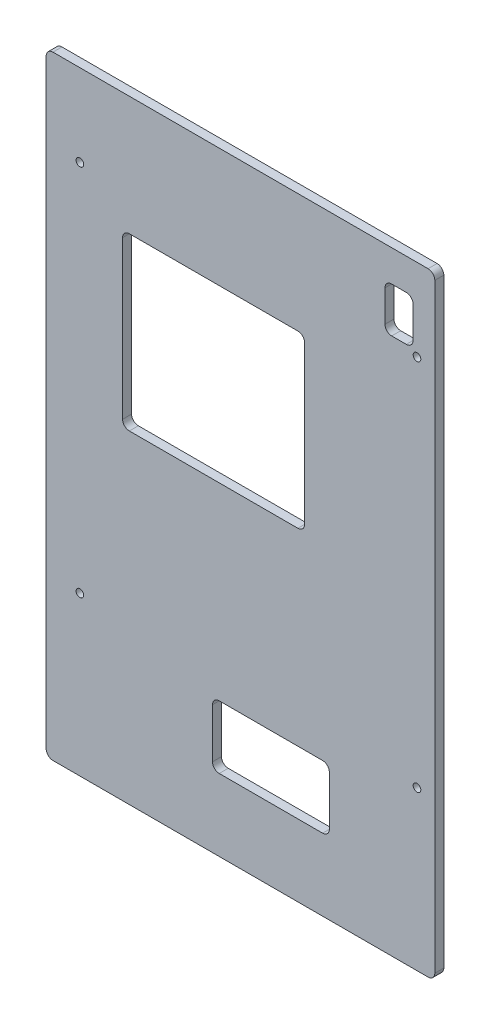
SolidWorks part; units mm, degrees
material "Verre"
ref_plane "Plan de face" through (0, 0, 0) normal (0, 0, 1) x (1, 0, 0)
ref_plane "Plan de dessus" through (0, 0, 0) normal (0, 1, 0) x (1, 0, 0)
ref_plane "Plan de droite" through (0, 0, 0) normal (1, 0, 0) x (0, 0, -1)
sketch "Esquisse1" plane through (0, 0, 0) normal (0, 0, 1) x (1, 0, 0)
  line L1 (0, 0) -> (172.93, 0)
  line L2 (0, 0) -> (0, 273)
  line L3 (0, 273) -> (172.93, 273)
  line L4 (172.93, 0) -> (172.93, 273)
  line L5 (74, 60) -> (126, 60)
  line L6 (74, 60) -> (74, 32)
  line L7 (74, 32) -> (126, 32)
  line L8 (126, 60) -> (126, 32)
  line L9 (34, 220) -> (115, 220)
  line L10 (34, 220) -> (34, 144)
  line L11 (34, 144) -> (115, 144)
  line L12 (115, 220) -> (115, 144)
  line L13 (163.25, 259) -> (150.75, 259)
  line L14 (163.25, 259) -> (163.25, 239)
  line L15 (163.25, 239) -> (150.75, 239)
  line L16 (150.75, 259) -> (150.75, 239)
  line L17 (163.25, 259) -> (150.75, 239) construction
  line L18 (163.25, 239) -> (150.75, 259) construction
  circle A0 centre (15, 236.5) radius 1.5
  circle A1 centre (165, 236.5) radius 1.5
  circle A2 centre (15, 70.5) radius 1.5
  circle A3 centre (165, 70.5) radius 1.5
  point P21 (157, 249)
  point P28 (161.179, 273)
  dimension "D5" = 3
  dimension "D8" = 3
  dimension "D11" = 3
  dimension "D22" = 3
  dimension "D25" = 12.5
  dimension "D1" = 172.93
  dimension "D2" = 273
  dimension "D3" = 36.5
  dimension "D4" = 15
  dimension "D6" = 7.93
  dimension "D7" = 36.5
  dimension "D9" = 70.5
  dimension "D10" = 15
  dimension "D12" = 74
  dimension "D13" = 52
  dimension "D14" = 28
  dimension "D15" = 32
  dimension "D16" = 34
  dimension "D17" = 81
  dimension "D18" = 144
  dimension "D19" = 76
  dimension "D20" = 7.93
  dimension "D21" = 70.5
  dimension "D23" = 15.93
  dimension "D24" = 24
  dimension "D26" = 20
extrude "Boss.-Extru.1" add sketch "Esquisse1" along normal blind 4
hole_wizard "Dégagement M31" positions "Esquisse2" profile "Esquisse3" hole size "M3" standard "ISO" end condition through all
sketch "Esquisse2" plane through (0, 0, 4) normal (0, 0, 1) x (1, 0, 0)
  point P0 (15, 236.5)
  point P3 (15, 70.5)
  point P6 (165, 236.5)
  point P9 (165, 70.5)
sketch "Esquisse3" plane through (15, 236.5, 4) normal (1, 0, 0) x (0, -1, 0)
  line L0 (0, 0) -> (0, 4)
  line L1 (0, 4) -> (1.7, 4)
  line L2 (1.7, 4) -> (1.7, 0)
  line L5 (1.7, 0) -> (0, 0)
  line L11 (0, -6.35) -> (0, 107.95) construction
  dimension "Diamètre du perçage jusqu'au prochain" = 3.4
  dimension "Profondeur du perçage jusqu'au prochain" = 4
fillet "Congé1" radius 3 16 edges at (0, 0, 2) (172.93, 0, 2) (126, 32, 2) (74, 32, 2) (126, 60, 2) (74, 60, 2) (115, 144, 2) (34, 144, 2) (115, 220, 2) (34, 220, 2) (172.93, 273, 2) (0, 273, 2) (163.25, 239, 2) (163.25, 259, 2) (150.75, 259, 2) (150.75, 239, 2)
